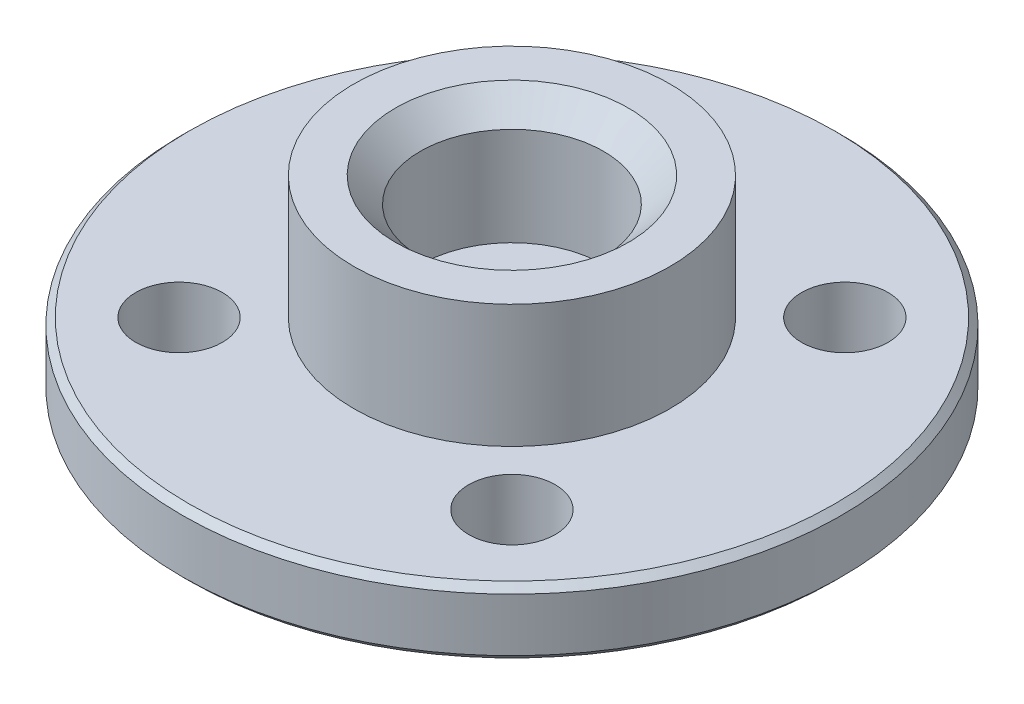
SolidWorks part; units mm, degrees
ref_plane "Front Plane" through (0, 0, 0) normal (0, 0, 1) x (1, 0, 0)
ref_plane "Top Plane" through (0, 0, 0) normal (0, 1, 0) x (1, 0, 0)
ref_plane "Right Plane" through (0, 0, 0) normal (1, 0, 0) x (0, 0, -1)
sketch "Sketch1" plane through (0, 0, 0) normal (0, 1, 0) x (1, 0, 0)
  circle A0 centre (0, 0) radius 9.9
  dimension "D1" = 19.8
extrude "Boss-Extrude1" add sketch "Sketch1" along normal blind 2 contours A0
sketch "Sketch2" plane through (0, 2, 0) normal (0, 1, 0) x (1, 0, 0)
  circle A0 centre (0, 0) radius 4.75
  circle A1 centre (0, 0) radius 2.75
  point P5 (3.0237, -1.5941)
  dimension "D1" = 9.5
  dimension "D2" = 5.5
extrude "Boss-Extrude2" add sketch "Sketch2" along normal blind 3.7
sketch "Sketch3" plane through (0, 0, 0) normal (0, -1, 0) x (1, 0, 0)
  line L0 (-5, 5) -> (5, -5) construction
  line L1 (5, 5) -> (-5, -5) construction
  circle A0 centre (-5, 5) radius 1.3
  circle A1 centre (5, 5) radius 1.3
  circle A2 centre (-5, -5) radius 1.3
  circle A3 centre (5, -5) radius 1.3
  circle A4 centre (0, 0) radius 1.45
  point P11 (0, 0)
  point P12 (5, -5)
  dimension "D1" = 2.9
  dimension "D2" = 2.6
  dimension "D3" = 10
  dimension "D4" = 10
extrude "Cut-Extrude1" cut sketch "Sketch3" against normal up to next
chamfer "Chamfer1" distance 0.75 angle 45 1 edges at (0, 5.7, 2.75)
chamfer "Chamfer2" distance 0.2 angle 45 2 edges at (0, 0, 9.9) (0, 2, 9.9)
